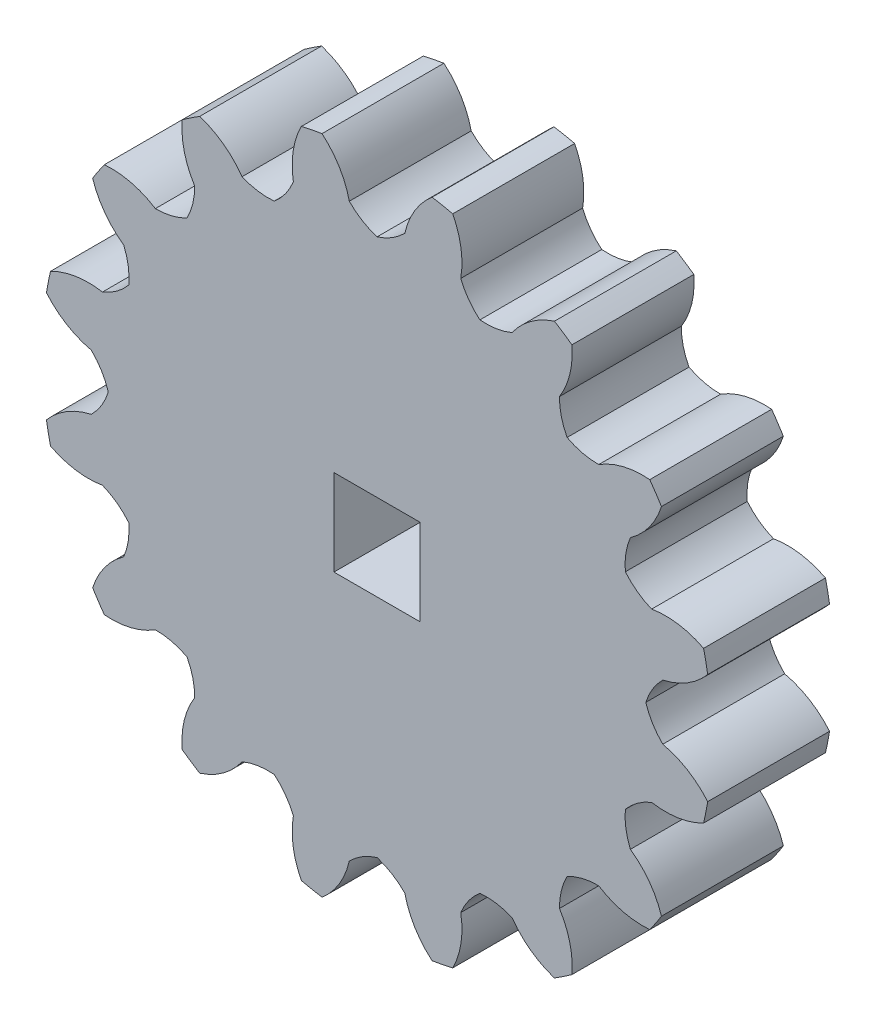
SolidWorks part; units mm, degrees
ref_plane "Front Plane" through (0, 0, 0) normal (0, 0, 1) x (1, 0, 0)
ref_plane "Top Plane" through (0, 0, 0) normal (0, 1, 0) x (1, 0, 0)
ref_plane "Right Plane" through (0, 0, 0) normal (1, 0, 0) x (0, 0, -1)
sketch "Sketch1" plane through (0, 0, 0) normal (0, 0, 1) x (1, 0, 0)
  line L1 (3.5355, -3.5355) -> (-3.5355, -3.5355)
  line L2 (3.5355, -3.5355) -> (3.5355, 3.5355)
  line L3 (3.5355, 3.5355) -> (-3.5355, 3.5355)
  line L4 (-3.5355, -3.5355) -> (-3.5355, 3.5355)
  line L5 (3.5355, -3.5355) -> (-3.5355, 3.5355) construction
  line L6 (3.5355, 3.5355) -> (-3.5355, -3.5355) construction
  circle A0 centre (0, 0) radius 27.5
  circle A1 centre (0, 0) radius 5 construction
  dimension "D1" = 55
  dimension "D2" = 10
extrude "Boss-Extrude1" add sketch "Sketch1" along normal blind 10
sketch "Sketch2" plane through (0, 0, 0) normal (0, 0, 1) x (1, 0, 0)
  line L1 (0, 0) -> (0, 31.514) construction
  arc A6 (0, 22.0495) -> (-2.278, 23.4413) centre (1.6105, 27.2457) cw
  arc A7 (-2.278, 23.4413) -> (-6.2846, 28.207) centre (-8.8939, 21.9463) ccw
  arc A8 (-6.2846, 28.207) -> (0, 31.514) centre (1.4962, 21.0454) cw
  arc A9 (6.2846, 28.207) -> (0, 31.514) centre (-1.4962, 21.0454) ccw
  arc A10 (2.278, 23.4413) -> (6.2846, 28.207) centre (8.8939, 21.9463) cw
  arc A11 (0, 22.0495) -> (2.278, 23.4413) centre (-1.6105, 27.2457) ccw
extrude "Cut-Extrude1" cut sketch "Sketch2" along normal through all
pattern_circular "CirPattern1" count 16 over 360 about axis through (0, 0, 10) along (0, 0, -1) of "Cut-Extrude1"
